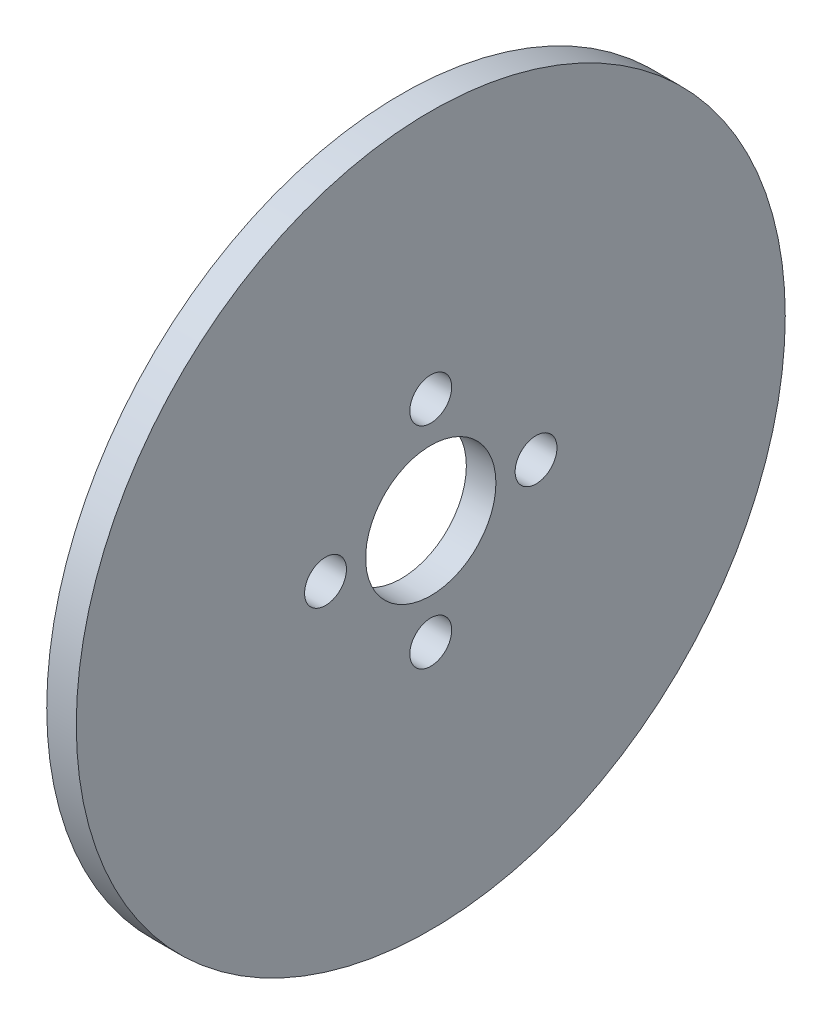
SolidWorks part; units mm, degrees
ref_plane "Front Plane" through (0, 0, 0) normal (1, 0, 0) x (0, 1, 0)
ref_plane "Top Plane" through (0, 0, 0) normal (0, 0, 1) x (0, 1, 0)
ref_plane "Right Plane" through (0, 0, 0) normal (0, 1, 0) x (-1, 0, 0)
sketch "Sketch1" plane through (0, 0, 0) normal (1, 0, 0) x (0, 1, 0)
  circle A0 centre (0, 0) radius 38.1
  circle A1 centre (0, 0) radius 7
  dimension "D1" = 76.2
  dimension "D2" = 14
extrude "Boss-Extrude2" add sketch "Sketch1" along normal blind 3.175
sketch "Sketch4" plane through (3.175, 0, 0) normal (1, 0, 0) x (0, 1, 0)
  line L0 (0, -11.3137) -> (-11.3137, 0) construction
  line L1 (0, -11.3137) -> (11.3137, 0) construction
  line L2 (-11.3137, 0) -> (0, 11.3137) construction
  line L3 (11.3137, 0) -> (0, 11.3137) construction
  line L4 (0, -11.3137) -> (0, 11.3137) construction
  line L5 (-11.3137, 0) -> (11.3137, 0) construction
  line L7 (-4, 19.3137) -> (4, 19.3137) construction
  line L8 (-4, 19.3137) -> (-4, 7.3137) construction
  line L9 (-4, 7.3137) -> (4, 7.3137) construction
  line L10 (4, 19.3137) -> (4, 7.3137) construction
  circle A0 centre (0, 11.3137) radius 2.25
  circle A1 centre (11.3137, 0) radius 2.25
  circle A2 centre (-11.3137, 0) radius 2.25
  circle A3 centre (0, -11.3137) radius 2.25
  circle A4 centre (0, 0) radius 20.574 construction
  point P1 (0, 0)
  point P14 (0, 19.3137)
  dimension "D2" = 4.5
  dimension "D6" = 41.148
  dimension "D1" = 16
  dimension "D3" = 8
  dimension "D4" = 12
  dimension "D5" = 8
extrude "Cut-Extrude3" cut sketch "Sketch4" against normal blind 30.394
